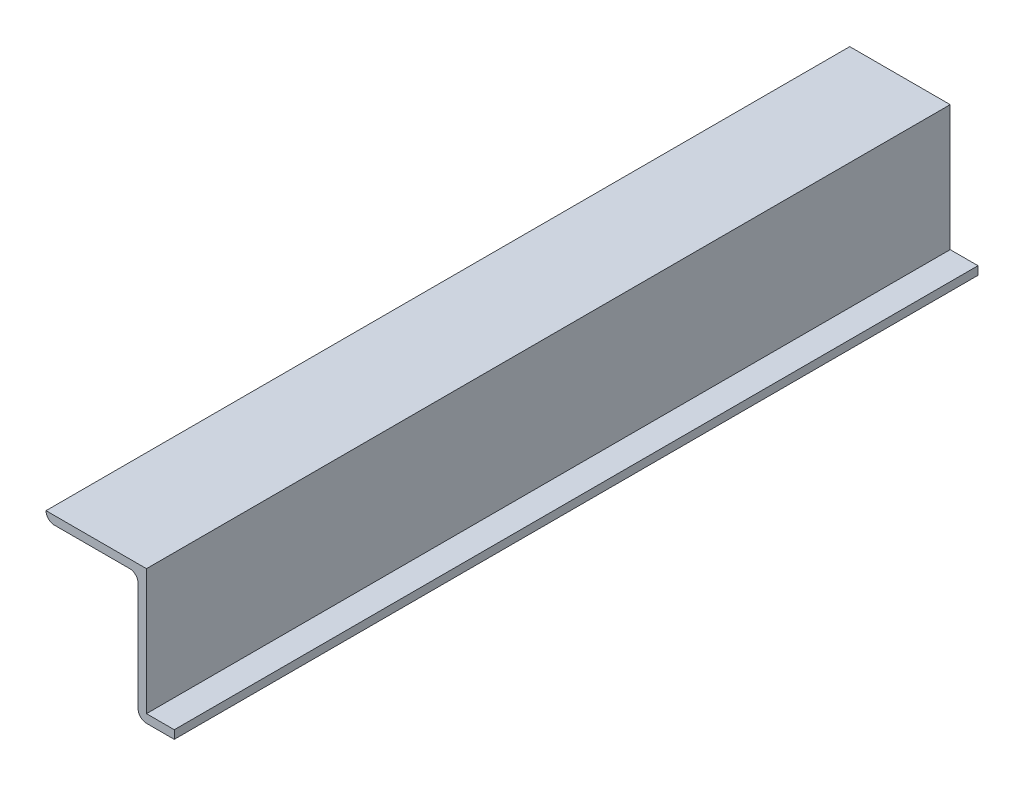
SolidWorks part; units mm, degrees
ref_plane "Front Plane" through (0, 0, 0) normal (0, 0, 1) x (1, 0, 0)
ref_plane "Top Plane" through (0, 0, 0) normal (0, 1, 0) x (1, 0, 0)
ref_plane "Right Plane" through (0, 0, 0) normal (1, 0, 0) x (0, 0, -1)
sketch "Sketch1" plane through (0, 0, 0) normal (0, 0, 1) x (1, 0, 0)
  line L0 (0, 0) -> (0, 47.625) construction
  line L1 (0, 47.625) -> (-34.925, 47.625) construction
  line L7 (-34.925, 47.625) -> (-34.925, 50.8) construction
  line L8 (-34.925, 50.8) -> (3.175, 50.8) construction
  line L13 (3.175, 50.8) -> (3.175, 3.175) construction
  line L14 (3.175, 3.175) -> (38.1, 3.175) construction
  line L15 (38.1, 3.175) -> (38.1, 0) construction
  line L16 (38.1, 0) -> (0, 0) construction
  line L17 (0, 47.625) -> (3.175, 47.625) construction
  point P2 (-34.925, 49.2125)
  dimension "Wall Thickness" = 3.175
  dimension "Outside Width" = 38.1
  dimension "Outside Height" = 50.8
sketch "Sketch2" plane through (0, 0, 0) normal (1, 0, 0) x (0, 0, -1)
  line L0 (152.4, 50.8) -> (-152.4, 50.8) construction
  point P3 (-108.585, 50.8)
  point P4 (0, 50.8)
  point P5 (108.585, 50.8)
  dimension "D1" = 43.815
  dimension "D2" = 43.815
  dimension "Length" = 304.8
sketch "Sketch3" plane through (0, 0, 0) normal (0, 0, 1) x (1, 0, 0)
  line L3 (-34.925, 50.8) -> (3.175, 50.8)
  line L17 (3.175, 50.8) -> (3.175, 3.175)
  line L21 (0, 0) -> (0, 47.625)
  line L22 (0, 47.625) -> (-34.925, 47.625)
  line L23 (-34.925, 47.625) -> (-34.925, 50.8)
  line L24 (3.175, 3.175) -> (13.716, 3.175)
  line L25 (0, 0) -> (13.716, 0)
  line L26 (13.716, 0) -> (13.716, 3.175)
extrude "Boss-Extrude1" add sketch "Sketch3" along normal mid plane 304.8
fillet "Fillet1" radius 3.175 3 edges at (-34.925, 47.625, 0) (0, 47.625, 0) (0, 0, 0)
equation "\"D1@Boss-Extrude1\" = \"Length@Sketch2\""
equation "\"D1@Sketch2\" = \"Outside Width@Sketch1\" * 1.15"
equation "\"D2@Sketch2\"=\"D1@Sketch2\""
equation "\"D1@Fillet1\"=\"Wall Thickness@Sketch1\""
